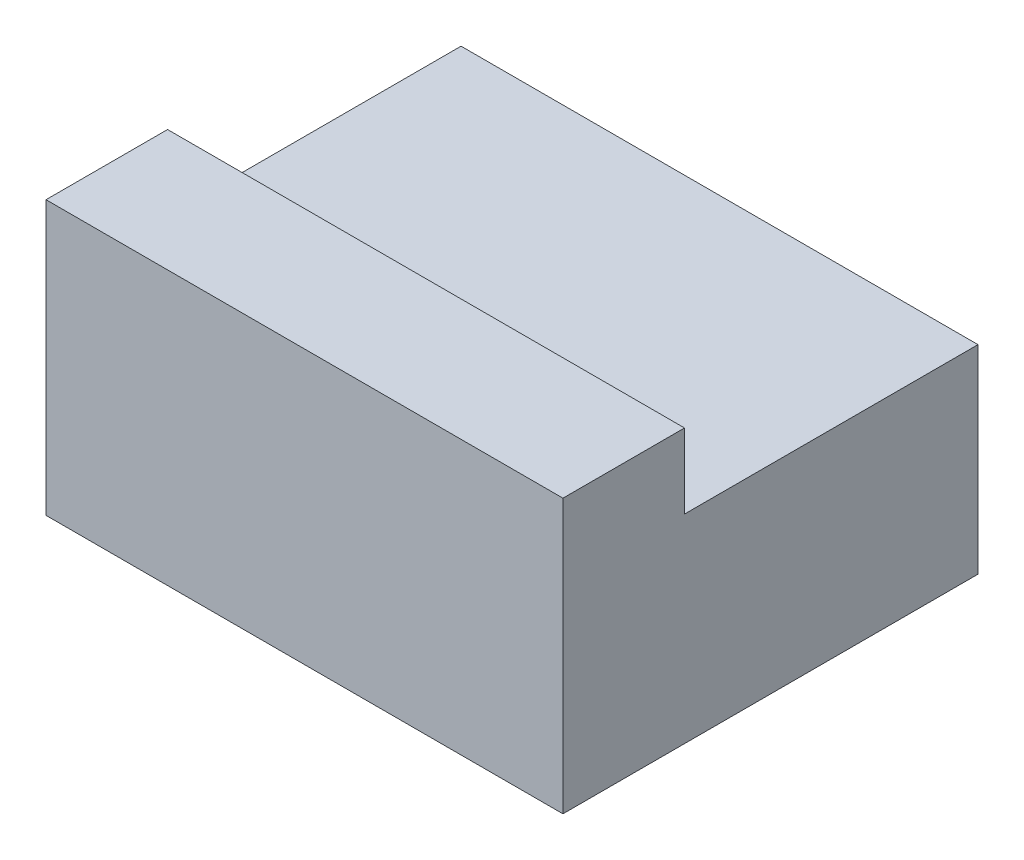
SolidWorks part; units mm, degrees
ref_plane "Front Plane" through (0, 0, 0) normal (0, 0, 1) x (1, 0, 0)
ref_plane "Top Plane" through (0, 0, 0) normal (0, 1, 0) x (1, 0, 0)
ref_plane "Right Plane" through (0, 0, 0) normal (1, 0, 0) x (0, 0, -1)
sketch "Sketch1" plane through (0, 0, 0) normal (0, 1, 0) x (1, 0, 0)
  line L1 (0, 0) -> (104, 0)
  line L2 (0, 0) -> (0, 83.5)
  line L3 (0, 83.5) -> (104, 83.5)
  line L4 (104, 0) -> (104, 83.5)
  dimension "D1" = 104
  dimension "D2" = 83.5
extrude "Boss-Extrude1" add sketch "Sketch1" along normal blind 55
sketch "Sketch2" plane through (104, 0, 0) normal (1, 0, 0) x (0, 0, -1)
  line L0 (0, 0) -> (83.5, 0) construction
  line L1 (83.5, 55) -> (24.4578, 55)
  line L2 (83.5, 55) -> (83.5, 40)
  line L3 (83.5, 40) -> (24.4578, 40)
  line L4 (24.4578, 55) -> (24.4578, 40)
  dimension "D1" = 40
extrude "Cut-Extrude1" cut sketch "Sketch2" against normal through all
